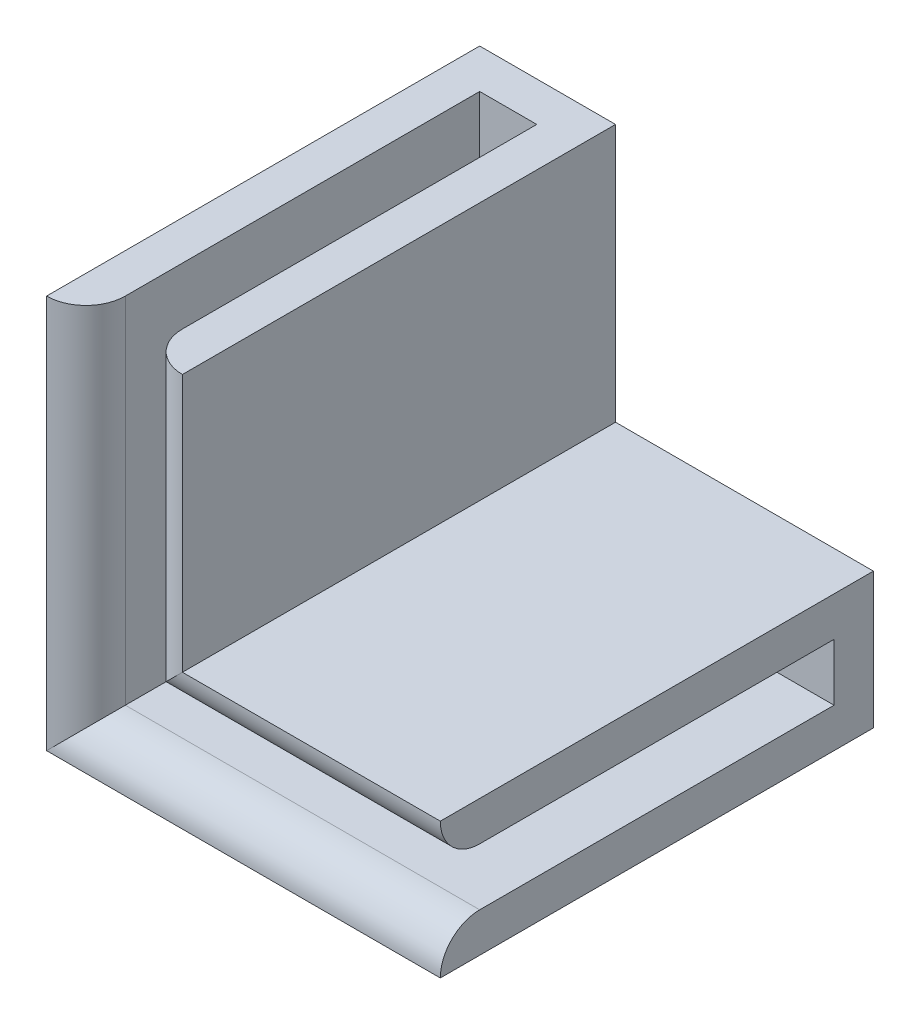
SolidWorks part; units mm, degrees
ref_plane "前视基准面" through (0, 0, 0) normal (0, 0, 1) x (1, 0, 0)
ref_plane "上视基准面" through (0, 0, 0) normal (0, 1, 0) x (1, 0, 0)
ref_plane "右视基准面" through (0, 0, 0) normal (1, 0, 0) x (0, 0, -1)
sketch "草图1" plane through (0, 0, 0) normal (0, 0, 1) x (1, 0, 0)
  line L1 (0, 0) -> (20, 0)
  line L2 (0, 0) -> (0, 2)
  line L3 (0, 2) -> (20, 2)
  line L4 (20, 0) -> (20, 2)
  line L5 (0, 0) -> (2, 0)
  line L6 (0, 0) -> (0, 20)
  line L7 (0, 20) -> (2, 20)
  line L8 (2, 0) -> (2, 20)
  line L9 (20, 4.9) -> (4.9, 4.9)
  line L10 (20, 4.9) -> (20, 6.9)
  line L11 (20, 6.9) -> (4.9, 6.9)
  line L12 (4.9, 4.9) -> (4.9, 6.9)
  line L13 (4.9, 4.9) -> (6.9, 4.9)
  line L14 (4.9, 4.9) -> (4.9, 20)
  line L15 (4.9, 20) -> (6.9, 20)
  line L16 (6.9, 4.9) -> (6.9, 20)
  dimension "D1" = 2
  dimension "D2" = 2
  dimension "D3" = 20
  dimension "D4" = 20
  dimension "D5" = 2
  dimension "D6" = 2
  dimension "D7" = 2.9
  dimension "D8" = 2.9
extrude "凸台-拉伸1" add sketch "草图1" along normal blind 20 contours L16 L9 L10 L11 | L9 L16 L11 L12 | L11 L16 L15 L14 | L3 L8 L7 L6 | L1 L8 L3 L2 | L8 L1 L4 L3 region at (1, 1, 0) region at (11, 1, 0) region at (1, 11, 0) region at (13.45, 5.9, 0) region at (5.9, 5.9, 0) region at (5.9, 13.45, 0)
sketch "草图2" plane through (0, 0, 0) normal (0, 0, -1) x (-1, 0, 0)
  line L0 (0, 0) -> (0, 20) construction
  line L1 (0, 20) -> (-2, 20) construction
  line L2 (-2, 20) -> (-2, 2) construction
  line L3 (-2, 2) -> (-20, 2) construction
  line L4 (-20, 2) -> (-20, 0) construction
  line L5 (-20, 0) -> (0, 0) construction
  line L6 (-6.9, 6.9) -> (-20, 6.9) construction
  line L7 (-20, 6.9) -> (-20, 4.9) construction
  line L8 (-20, 4.9) -> (-4.9, 4.9) construction
  line L9 (-4.9, 4.9) -> (-4.9, 20) construction
  line L10 (-4.9, 20) -> (-6.9, 20) construction
  line L11 (-6.9, 20) -> (-6.9, 6.9) construction
  line L12 (0, 0) -> (0, 20)
  line L13 (0, 20) -> (-2, 20)
  line L14 (-2, 20) -> (-2, 2)
  line L15 (-2, 2) -> (-20, 2)
  line L16 (-20, 2) -> (-20, 0)
  line L17 (-20, 0) -> (0, 0)
  line L18 (-6.9, 6.9) -> (-20, 6.9)
  line L19 (-20, 6.9) -> (-20, 4.9)
  line L20 (-20, 4.9) -> (-4.9, 4.9)
  line L21 (-4.9, 4.9) -> (-4.9, 20)
  line L22 (-4.9, 20) -> (-6.9, 20)
  line L23 (-6.9, 20) -> (-6.9, 6.9)
  line L24 (-20, 4.9) -> (-20, 2)
  line L25 (-4.9, 20) -> (-2, 20)
  line M1 (-6.9, 6.9) -> (-20, 6.9)
  line M2 (-20, 6.9) -> (-20, 4.9)
  line M3 (-20, 4.9) -> (-4.9, 4.9)
  line M4 (-4.9, 4.9) -> (-4.9, 20)
  line M5 (-4.9, 20) -> (-6.9, 20)
  line M6 (-6.9, 20) -> (-6.9, 6.9)
extrude "凸台-拉伸2" add sketch "草图2" along normal blind 2 contours L25 L24 L15 L14 M4 M3 | M6 M1 M2 M3 M4 M5 | L16 L17 L12 L13 L14 L15 region at (10, 0.2828, 0) region at (2.2546, 11, 0) region at (5.1135, 12.45, 0)
fillet "圆角1" radius 2 4 edges at (12.45, 4.9, 20) (11, 2, 20) (4.9, 12.45, 20) (2, 11, 20)
